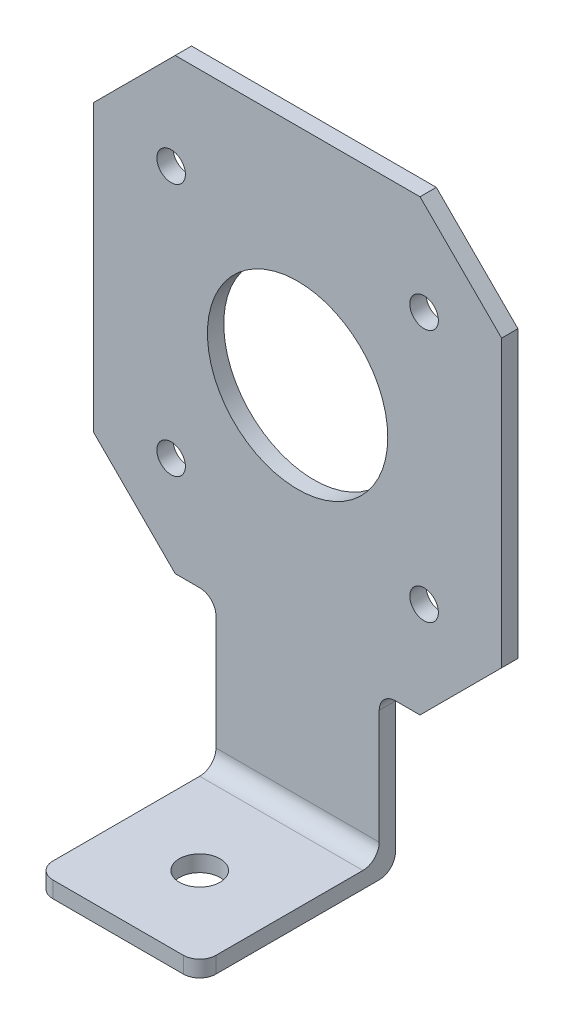
SolidWorks part; units mm, degrees
material "PLA"
ref_plane "Piano frontale" through (0, 0, 0) normal (0, 0, 1) x (1, 0, 0)
ref_plane "Piano superiore" through (0, 0, 0) normal (0, 1, 0) x (1, 0, 0)
ref_plane "Piano destro" through (0, 0, 0) normal (1, 0, 0) x (0, 0, -1)
sketch "Schizzo1" plane through (0, 0, 0) normal (0, 0, 1) x (1, 0, 0)
  line L5 (0, 0) -> (0, -67.5867) construction
  line L6 (-25, -27.5) -> (-10, -27.5)
  line L10 (-25, -27.5) -> (-25, 27.5)
  line L11 (-15.5, 15.5) -> (15.5, 15.5) construction
  line L12 (-15.5, 15.5) -> (-15.5, -15.5) construction
  line L13 (-15.5, -15.5) -> (15.5, -15.5) construction
  line L14 (15.5, 15.5) -> (15.5, -15.5) construction
  line L15 (-15.5, 15.5) -> (15.5, -15.5) construction
  line L16 (-15.5, -15.5) -> (15.5, 15.5) construction
  line L17 (-25, 27.5) -> (25, 27.5)
  line L18 (25, -27.5) -> (25, 27.5)
  line L22 (-25, -27.5) -> (25, 27.5) construction
  line L27 (-25, 27.5) -> (25, -27.5) construction
  line L29 (-10, -47.5) -> (10, -47.5)
  line L31 (-10, -47.5) -> (-10, -27.5)
  line L33 (10, -47.5) -> (10, -27.5)
  line L34 (-10, -47.5) -> (10, -27.5) construction
  line L35 (-10, -27.5) -> (10, -47.5) construction
  line L36 (10, -27.5) -> (25, -27.5)
  circle A0 centre (-15.5, 15.5) radius 1.75
  circle A1 centre (15.5, 15.5) radius 1.75
  circle A2 centre (15.5, -15.5) radius 1.75
  circle A3 centre (-15.5, -15.5) radius 1.75
  circle A4 centre (0, 0) radius 11.05
  point P4 (0, -37.5)
  point P14 (0, 0)
  dimension "D10" = 3.5
  dimension "D11" = 22.1
  dimension "D2" = 50
  dimension "D4" = 20
  dimension "D3" = 55
  dimension "D8" = 31
  dimension "D5" = 20
extrude "Estrusione-Estrusione1" add sketch "Schizzo1" along normal blind 2
sketch "Schizzo14" plane through (0, 0, 2) normal (0, 0, 1) x (1, 0, 0)
  line L0 (10, -47.5) -> (10, -27.5) construction
  line L1 (-10, -47.5) -> (10, -47.5)
  line L2 (-10, -47.5) -> (-10, -45.5)
  line L3 (-10, -45.5) -> (10, -45.5)
  line L4 (10, -47.5) -> (10, -45.5)
  dimension "D1" = 2
extrude "Estrusione-Estrusione2" add sketch "Schizzo14" along normal blind 22
sketch "Schizzo15" plane through (0, -45.5, 0) normal (0, 1, 0) x (1, 0, 0)
  line L0 (25, -2) -> (-25, -2) construction
  circle A0 centre (0, -14) radius 2.5
  point P4 (0, 0)
  dimension "D1" = 5
  dimension "D2" = 12
extrude "Taglio-Estrusione1" cut sketch "Schizzo15" against normal blind 10
chamfer "Smusso1" distance 10 angle 45 4 edges at (25, -27.5, 1) (-25, -27.5, 1) (-25, 27.5, 1) (25, 27.5, 1)
fillet "Raccordo1" radius 2 6 edges at (10, -46.5, 24) (-10, -46.5, 24) (0, -45.5, 2) (0, -47.5, 0) (-10, -27.5, 1) (10, -27.5, 1)
